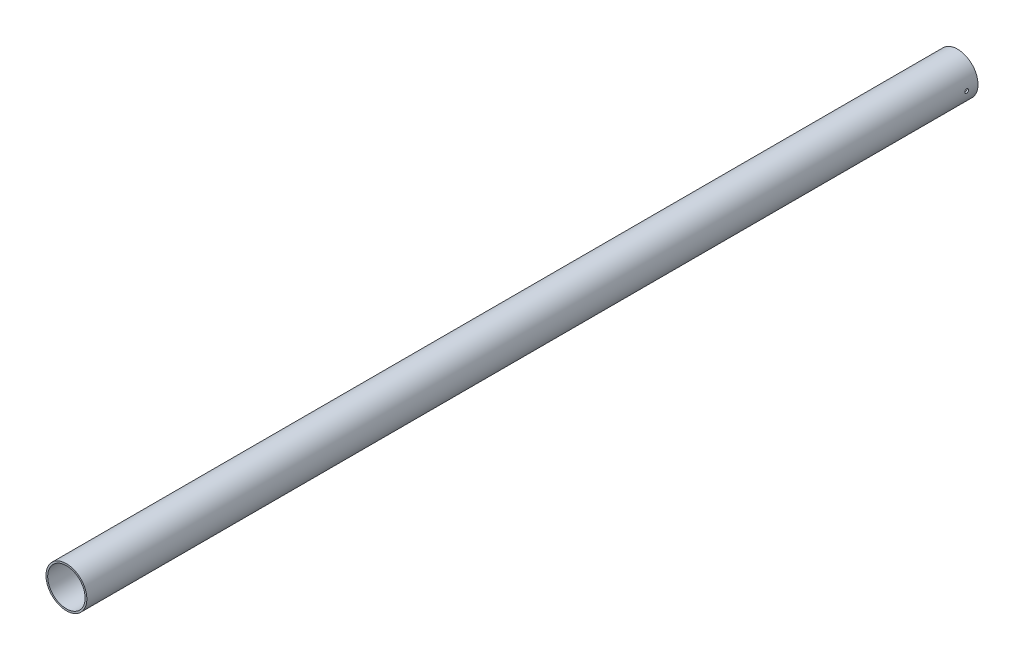
SolidWorks part; units mm, degrees
material "PC High Viscosity"
ref_plane "Front Plane" through (0, 0, 0) normal (0, 0, 1) x (1, 0, 0)
ref_plane "Top Plane" through (0, 0, 0) normal (0, 1, 0) x (1, 0, 0)
ref_plane "Right Plane" through (0, 0, 0) normal (1, 0, 0) x (0, 0, -1)
sketch "Sketch1" plane through (0, 0, 0) normal (0, 0, 1) x (1, 0, 0)
  circle A0 centre (0, 0) radius 12.7
  circle A1 centre (0, 0) radius 11.6205
  dimension "D1" = 25.4
  dimension "D2" = 23.241
extrude "Boss-Extrude1" add sketch "Sketch1" along normal blind 553.63
hole_wizard "M2 Clearance Hole1" positions "Sketch2" profile "Sketch3" hole size "M2" standard "ANSI Metric" end condition through all
sketch "Sketch2" plane through (0, 0, 0) normal (1, 0, 0) x (0, 0, -1)
  line L1 (0, -12.7) -> (0, 12.7) construction
  point P0 (-7, 0)
  point P7 (0, 0)
  dimension "D1" = 7
sketch "Sketch3" plane through (0, 0, 7) normal (0, 1, 0) x (0, 0, 1)
  line L0 (0, 0) -> (0, 12.7)
  line L1 (0, 12.7) -> (1.2, 12.7)
  line L2 (1.2, 12.7) -> (1.2, 0)
  line L5 (1.2, 0) -> (0, 0)
  line L11 (0, -6.35) -> (0, 107.95) construction
  dimension "Thru Hole Dia." = 2.4
  dimension "Thru Hole Depth" = 12.7
mirror "Mirror1" about plane through (0, 0, 0) normal (1, 0, 0) of "M2 Clearance Hole1"
